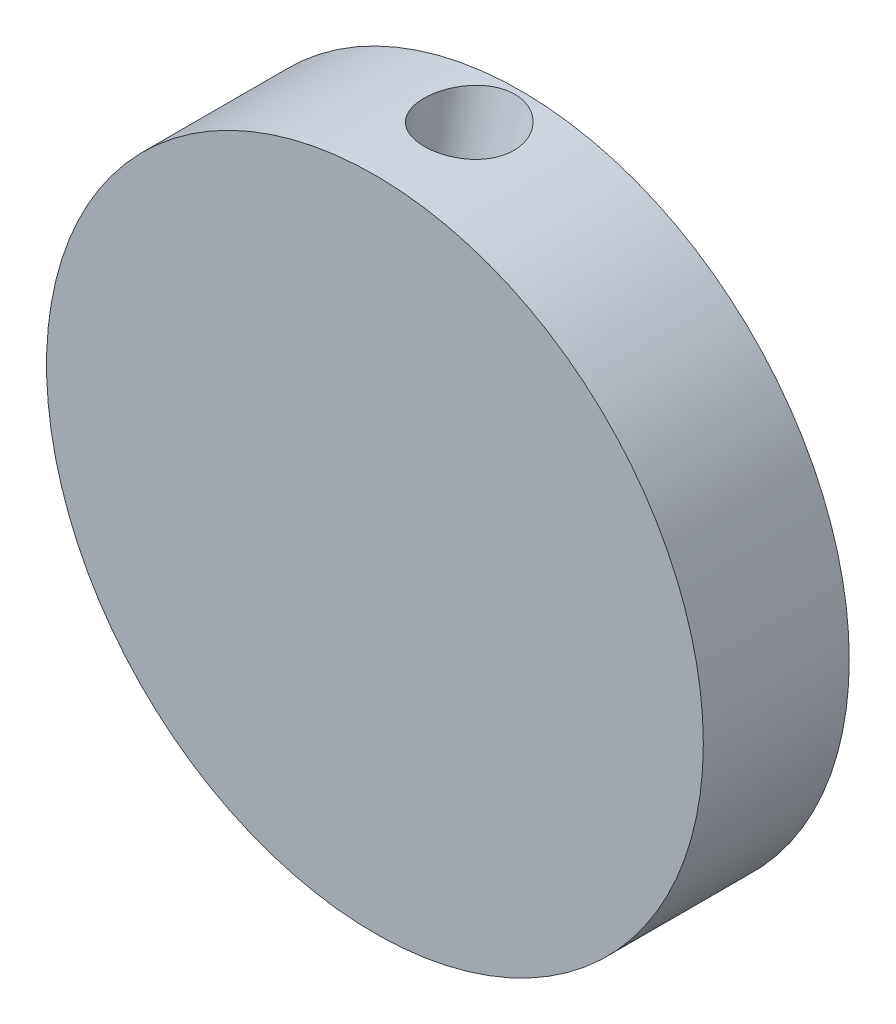
SolidWorks part; units mm, degrees
ref_plane "Front Plane" through (0, 0, 0) normal (1, 0, 0) x (0, 1, 0)
ref_plane "Top Plane" through (0, 0, 0) normal (0, 0, 1) x (0, 1, 0)
ref_plane "Right Plane" through (0, 0, 0) normal (0, 1, 0) x (-1, 0, 0)
sketch "Sketch1" plane through (0, 0, 0) normal (0, 0, 1) x (0, 1, 0)
  circle A0 centre (0, 0) radius 22.5
  dimension "D1" = 45
extrude "Boss-Extrude1" add sketch "Sketch1" along normal blind 10
ref_plane "Plane1" through (0, 22.5, 0) normal (0, 1, 0) x (-1, 0, 0)
sketch "Sketch3" plane through (0, 22.5, 0) normal (0, 1, 0) x (-1, 0, 0)
  line L0 (0, 14.064) -> (0, 0) construction
  line L1 (-22.5, 0) -> (22.5, 0) construction
  line L2 (0, 7.032) -> (0, 0) construction
  circle A0 centre (0, 3.516) radius 3.1
  point P7 (0, 3.7082)
  point P8 (0, 3.8509)
  point P9 (0, 0)
  point P10 (0, 0)
  point P11 (0, 3.516)
  dimension "D1" = 6.2
ref_plane "Plane3" through (0, 6.5, 0) normal (0, 1, 0) x (-1, 0, 0)
sketch "Sketch8" plane through (0, 6.5, 0) normal (0, 1, 0) x (-1, 0, 0)
  circle A0 centre (0, 7.032) radius 2.8
  dimension "D1" = 5.6
loft "Cut-Loft2" cut profiles "Sketch3", "Sketch8" connector at (-3.0627, 22.5, 3.9952) connector at (-2.4811, 6.5, 5.7343)
